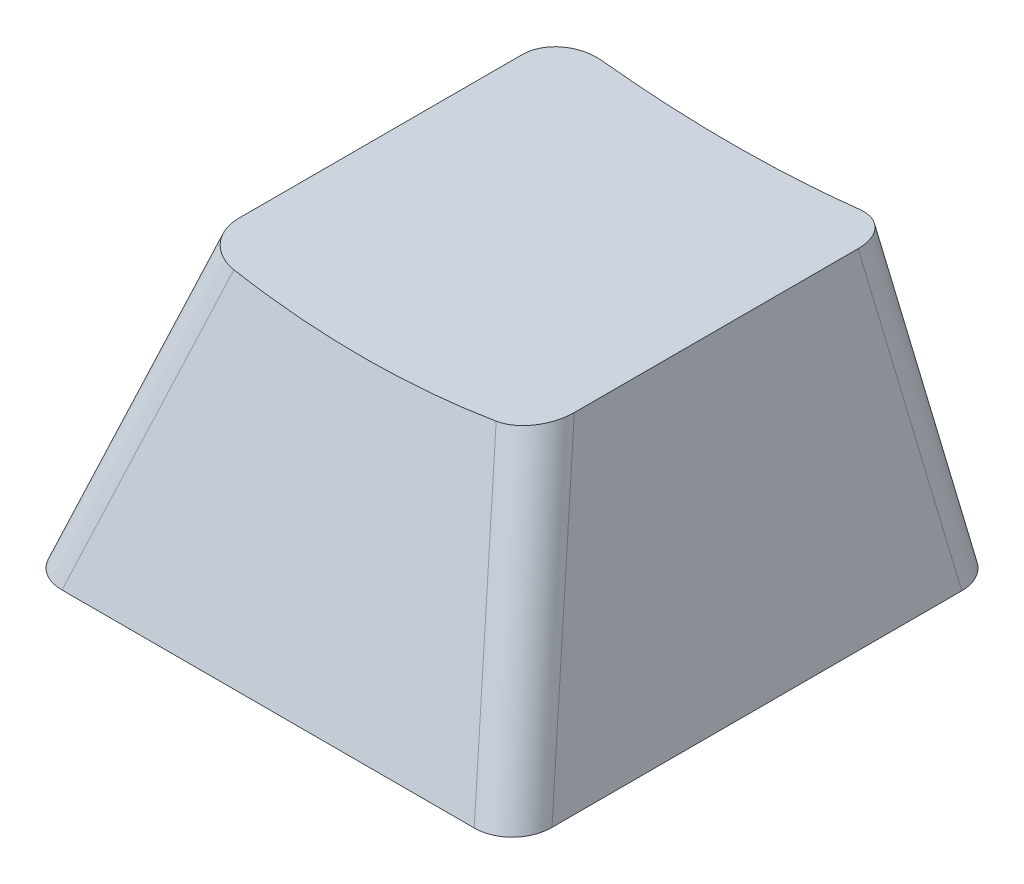
SolidWorks part; units mm, degrees
ref_plane "Спереди" through (0, 0, 0) normal (0, 0, 1) x (1, 0, 0)
ref_plane "Сверху" through (0, 0, 0) normal (0, 1, 0) x (1, 0, 0)
ref_plane "Справа" through (0, 0, 0) normal (1, 0, 0) x (0, 0, -1)
sketch "Эскиз1" plane through (0, 0, 0) normal (0, 1, 0) x (1, 0, 0)
  line L1 (-9, -9) -> (9, -9)
  line L2 (-9, -9) -> (-9, 9)
  line L3 (-9, 9) -> (9, 9)
  line L4 (9, -9) -> (9, 9)
  line L5 (-9, -9) -> (9, 9) construction
  line L6 (-9, 9) -> (9, -9) construction
  point P0 (0, 0)
  dimension "D1" = 18
extrude "Бобышка-Вытянуть1" add sketch "Эскиз1" along normal blind 10
sketch "Эскиз2" plane through (0, 0, 9) normal (0, 0, 1) x (1, 0, 0)
  line L0 (0, 0) -> (0, 10) construction
  line L1 (-9, 0) -> (9, 0) construction
  line L2 (-9, 10) -> (9, 10) construction
  line L3 (-9, 0) -> (-9, 10)
  line L4 (-9, 10) -> (-6.185, 10)
  line L5 (-6.185, 10) -> (-9, 0)
  line L6 (6.185, 10) -> (9, 0)
  line L7 (9, 10) -> (6.185, 10)
  line L8 (9, 0) -> (9, 10)
  dimension "D1" = 12.37
extrude "Вырез-Вытянуть1" cut sketch "Эскиз2" against normal up to next
sketch "Эскиз3" plane through (0, 0, 0) normal (1, 0, 0) x (0, 0, -1)
  line L0 (-9, 0) -> (-9, 10)
  line L1 (-9, 10) -> (-5.3603, 10)
  line L2 (9, 10) -> (-9, 10) construction
  line L3 (-5.3603, 10) -> (-9, 0)
  line L4 (8, 10) -> (9, 10)
  line L5 (9, 10) -> (9, 0)
  line L6 (9, 0) -> (8, 10)
  line L7 (-9, 0) -> (9, 0) construction
  dimension "D1" = 1
  dimension "D2" = 70
extrude "Вырез-Вытянуть2" cut sketch "Эскиз3" against normal through all both and the other way through all
sketch "Эскиз4" plane through (0, 0, 0) normal (0, 0, 1) x (1, 0, 0)
  line L0 (-6.185, 10) -> (6.185, 10) construction
  line L1 (-6.185, 10) -> (6.185, 10)
  arc A0 (-6.185, 10) -> (6.185, 10) centre (0, 48.0042) ccw
  point P1 (0, 9.5)
  dimension "D1" = 0.5
extrude "Вырез-Вытянуть3" cut sketch "Эскиз4" against normal through all both and the other way through all
fillet "Скругление1" radius 1.5 4 edges at (7.5925, 5, 7.1801) (7.5925, 5, -8.5) (-7.5925, 5, -8.5) (-7.5925, 5, 7.1801)
shell "Оболочка1" thickness 2 removed face at (0, 0, 0.005)
fillet "Скругление2" radius 0.5 4 edges at (5.8276, 3.8887, -6.6012) (-5.8276, 3.8887, -6.6012) (5.8276, 3.8887, 5.4563) (-5.8276, 3.8887, 5.4563)
sketch "Эскиз5" plane through (0, 0, 0) normal (0, -1, 0) x (1, 0, 0)
  line L0 (0, 0) -> (0, 2) construction
  line L1 (0, 0) -> (-2, 0) construction
  line L2 (0.6, 2) -> (-0.6, 2) construction
  line L3 (-0.6, 2) -> (-0.6, 0.6) construction
  line L4 (-0.6, 0.6) -> (-2, 0.6) construction
  line L5 (2, 0.6) -> (0.6, 0.6) construction
  line L6 (2, -0.6) -> (2, 0.6) construction
  line L7 (0.6, 0.6) -> (0.6, 2) construction
  line L8 (0.6, -2) -> (0.6, -0.6) construction
  line L9 (-0.6, -2) -> (0.6, -2) construction
  line L10 (0.6, -0.6) -> (2, -0.6) construction
  line L11 (-2, -0.6) -> (-0.6, -0.6) construction
  line L12 (-2, 0.6) -> (-2, -0.6) construction
  line L13 (-0.6, -0.6) -> (-0.6, -2) construction
  line L14 (-3.5, -2.5) -> (3.5, -2.5) construction
  line L15 (-3.5, -2.5) -> (-3.5, 2.5) construction
  line L16 (-3.5, 2.5) -> (3.5, 2.5) construction
  line L17 (3.5, -2.5) -> (3.5, 2.5) construction
  point P3 (-2, 0)
  point P4 (0, 0)
  point P8 (0, 0)
  point P13 (-3.5, 0)
  point P15 (0, 2.5)
  point P28 (0, 0)
  dimension "D2" = 1.2
  dimension "D3" = 4
  dimension "D4" = 5
  dimension "D5" = 7
  dimension "D1" = 4
sketch "Эскиз6" plane through (0, 0, 0) normal (0, -1, 0) x (1, 0, 0)
  line L0 (-3.5, 2.5) -> (-3.5, -2.5) construction
  line L1 (-3.5, -2.5) -> (-0.6, -2.5) construction
  line L2 (-3.5, -2.5) -> (3.5, -2.5) construction
  line L3 (-0.6, -2.5) -> (-0.6, -0.6) construction
  line L4 (-0.6, -0.6) -> (-2, -0.6) construction
  line L5 (-2, -0.6) -> (-2, 0.6) construction
  line L6 (-2, 0.6) -> (-0.6, 0.6) construction
  line L7 (-0.6, 0.6) -> (-0.6, 2.5) construction
  line L8 (-3.5, 2.5) -> (3.5, 2.5) construction
  line L9 (-0.6, 2.5) -> (-3.5, 2.5) construction
  line L10 (-3.25, 2.25) -> (-3.25, -2.25)
  line L11 (-3.25, -2.25) -> (-0.85, -2.25)
  line L12 (-0.85, -2.25) -> (-0.85, -0.85)
  line L13 (-0.85, -0.85) -> (-2.25, -0.85)
  line L14 (-2.25, -0.85) -> (-2.25, 0.85)
  line L15 (-2.25, 0.85) -> (-0.85, 0.85)
  line L16 (-0.85, 0.85) -> (-0.85, 2.25)
  line L17 (-0.85, 2.25) -> (-3.25, 2.25)
  line L18 (0, 0) -> (0, 2.6916) construction
  line L19 (3.25, -2.25) -> (0.85, -2.25)
  line L20 (0.85, -2.25) -> (0.85, -0.85)
  line L21 (0.85, -0.85) -> (2.25, -0.85)
  line L22 (2.25, -0.85) -> (2.25, 0.85)
  line L23 (2.25, 0.85) -> (0.85, 0.85)
  line L24 (0.85, 0.85) -> (0.85, 2.25)
  line L25 (0.85, 2.25) -> (3.25, 2.25)
  line L26 (3.25, 2.25) -> (3.25, -2.25)
  dimension "D1" = 0.25
extrude "Бобышка-Вытянуть2" add sketch "Эскиз6" against normal up to surface (7.5089 mm away) up to face at (-0.0019, 7.6998, -1.0706)
sketch "Эскиз7" plane through (0, 0, 0) normal (0, 0, 1) x (1, 0, 0)
  line L0 (-5.6555, 4.5) -> (-4.7329, 7.7775)
  line L1 (-4.7329, 7.7775) -> (-6.9223, 0) construction
  line L2 (0, 0) -> (0, 7.5) construction
  line L3 (5.6555, 4.5) -> (4.7329, 7.7775)
  line L4 (5.6555, 4.5) -> (-5.6555, 4.5)
  arc A1 (-4.7329, 7.7775) -> (4.7329, 7.7775) centre (0, 48.0042) ccw
  arc A2 (-4.276, 7.7263) -> (4.276, 7.7263) centre (0, 48.0042) ccw construction
  dimension "D1" = 4.5
extrude "Бобышка-Вытянуть3" add sketch "Эскиз7" along normal up to surface and the other way up to surface up to face at (0, 3.8066, 5.4862) other way up to face at (0, 3.8057, -6.6095)
fillet "Скругление3" radius 0.5 14 edges at (5.5083, 4.5, -6.3976) (5.6555, 4.5, -0.65) (5.52, 4.5, 5.095) (0, 4.5, 5.2338) (-5.52, 4.5, 5.095) (-5.6555, 4.5, -0.65) (-5.5083, 4.5, -6.3976) (0, 4.5, -6.54) (-2.05, 4.5, -2.25) (-3.25, 4.5, 0) (-2.05, 4.5, 2.25) (2.05, 4.5, 2.25) (3.25, 4.5, 0) (2.05, 4.5, -2.25)
